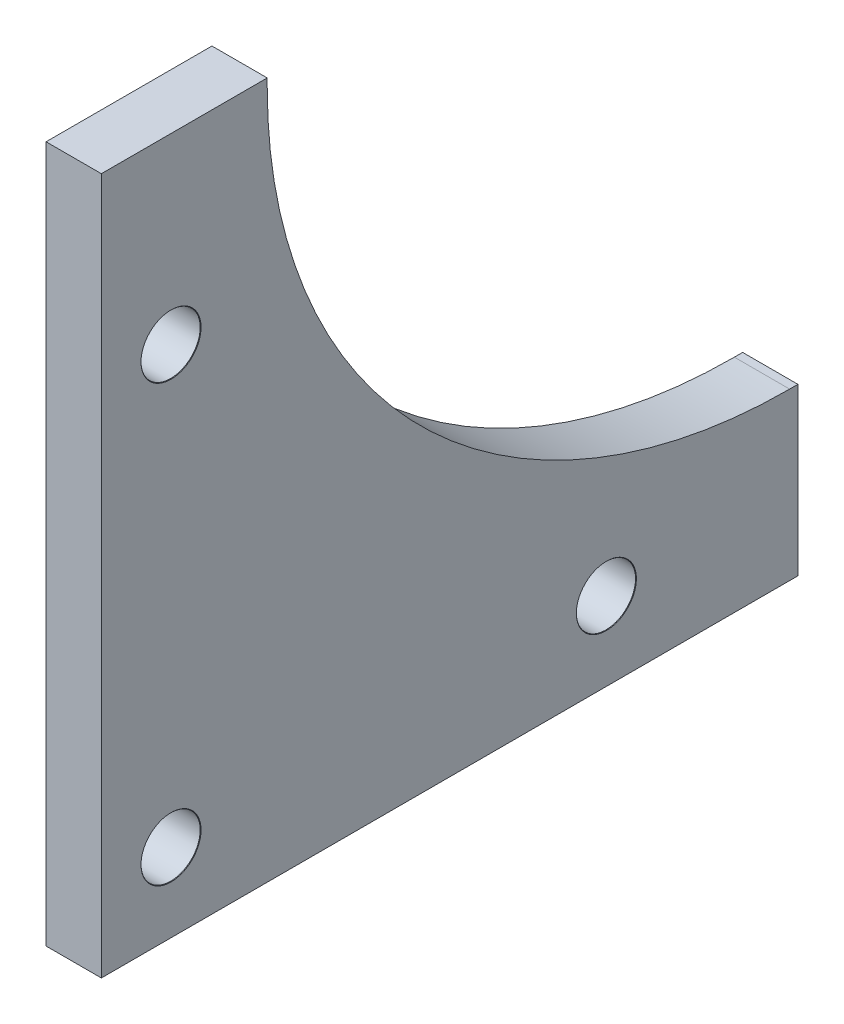
SolidWorks part; units mm, degrees
material "1060 Alloy"
ref_plane "Front Plane" through (0, 0, 0) normal (0, 0, 1) x (1, 0, 0)
ref_plane "Top Plane" through (0, 0, 0) normal (0, 1, 0) x (1, 0, 0)
ref_plane "Right Plane" through (0, 0, 0) normal (1, 0, 0) x (0, 0, -1)
sketch "Sketch1" plane through (0, 0, 0) normal (1, 0, 0) x (0, 0, -1)
  line L0 (0, 0) -> (0, 40)
  line L2 (40, 0) -> (0, 0)
  line L3 (0, 40) -> (9.525, 40)
  line L4 (9.525, 40) -> (9.525, 9.525)
  line L5 (9.525, 9.525) -> (40, 9.525)
  line L6 (40, 9.525) -> (40, 0)
  dimension "D1" = 40
  dimension "D2" = 9.525
extrude "Boss-Extrude1" add sketch "Sketch1" along normal blind 3.175
sketch "Sketch6" plane through (3.175, 0, 0) normal (1, 0, 0) x (0, 0, -1)
  line L0 (4, 4.5) -> (4, 29.5) construction
  line L1 (4, 29.5) -> (29, 4.5) construction
  line L2 (29, 4.5) -> (4, 4.5) construction
  line L3 (0, 40) -> (0, 0) construction
  line L4 (0, 0) -> (40, 0) construction
  point P11 (4, 29.5)
  point P12 (29, 4.5)
  point P13 (4, 4.5)
  dimension "D1" = 4
  dimension "D2" = 25
  dimension "D3" = 4.5
hole_wizard "M3 Clearance Hole1" positions "Sketch7" profile "Sketch9" hole size "M3" standard "ANSI Metric" end condition through all
sketch "Sketch7" plane through (3.175, 0, 0) normal (1, 0, 0) x (0, 0, -1)
  point P0 (29, 4.5)
  point P3 (4, 29.5)
  point P6 (4, 4.5)
sketch "Sketch9" plane through (3.175, 4.5, -29) normal (0, 1, 0) x (0, 0, -1)
  line L0 (0, 0) -> (0, 3.175)
  line L1 (0, 3.175) -> (1.7, 3.175)
  line L2 (1.7, 3.175) -> (1.7, 0.025)
  line L3 (1.7, 0.025) -> (1.725, 0)
  line L5 (1.725, 0) -> (0, 0)
  line L6 (-1.7, 0.025) -> (-1.725, 0) construction
  line L11 (0, -6.35) -> (0, 107.95) construction
  dimension "Thru Hole Dia." = 3.4
  dimension "Thru Hole Depth" = 3.175
  dimension "Near C'Sink Dia." = 3.45
  dimension "Near C'Sink Angle" = 90
fillet "Fillet1" radius 30 1 edges at (1.5875, 9.525, -9.525)
